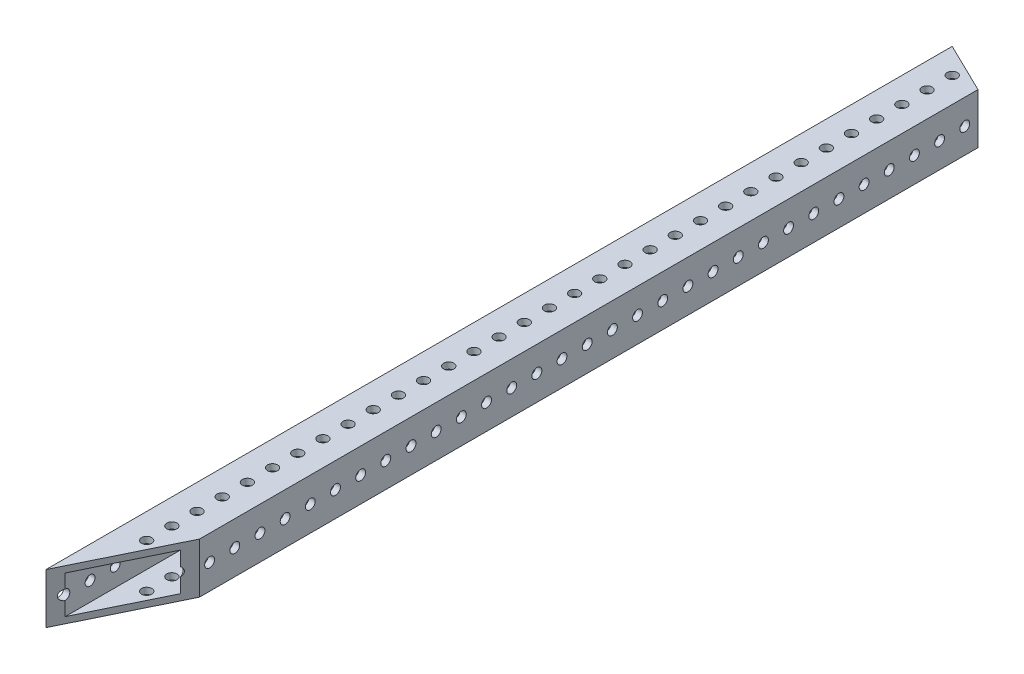
SolidWorks part; units mm, degrees
material "6061-T6 (SS)"
ref_plane "Front Plane" through (0, 0, 0) normal (0, 0, 1) x (1, 0, 0)
ref_plane "Top Plane" through (0, 0, 0) normal (0, 1, 0) x (1, 0, 0)
ref_plane "Right Plane" through (0, 0, 0) normal (1, 0, 0) x (0, 0, -1)
sketch "Sketch1" plane through (0, 0, 0) normal (0, 0, 1) x (1, 0, 0)
  line L0 (-9.525, 9.525) -> (9.525, 9.525)
  line L1 (-12.7, 12.7) -> (12.7, 12.7)
  line L2 (-12.7, 12.7) -> (-12.7, -12.7)
  line L3 (-12.7, -12.7) -> (12.7, -12.7)
  line L4 (12.7, 12.7) -> (12.7, -12.7)
  line L5 (9.525, 9.525) -> (9.525, -9.525)
  line L6 (-9.525, -9.525) -> (9.525, -9.525)
  line L7 (-9.525, 9.525) -> (-9.525, -9.525)
  line L8 (-12.7, 12.7) -> (12.7, -12.7) construction
  line L9 (12.7, 12.7) -> (-12.7, -12.7) construction
  point P5 (0, 0)
  dimension "D1" = 25.4
  dimension "D2" = 25.4
  dimension "D3" = 3.175
extrude "Boss-Extrude1" add sketch "Sketch1" along normal mid plane 457.2
sketch "Sketch2" plane through (0, 12.7, 0) normal (0, 1, 0) x (1, 0, 0)
  circle A2 centre (0, -292.1) radius 2.5527 construction
  circle A3 centre (0, -279.4) radius 2.5527 construction
  circle A6 centre (0, -266.7) radius 2.5527
  circle A9 centre (0, -254) radius 2.5527
  circle A12 centre (0, -241.3) radius 2.5527
  circle A15 centre (0, -228.6) radius 2.5527 construction
  circle A18 centre (0, -215.9) radius 2.5527 construction
  circle A21 centre (0, -203.2) radius 2.5527 construction
  circle A24 centre (0, -190.5) radius 2.5527
  circle A27 centre (0, -177.8) radius 2.5527
  circle A30 centre (0, -165.1) radius 2.5527
  circle A33 centre (0, -152.4) radius 2.5527
  circle A36 centre (0, -139.7) radius 2.5527
  circle A39 centre (0, -127) radius 2.5527
  circle A42 centre (0, -114.3) radius 2.5527
  circle A45 centre (0, -101.6) radius 2.5527
  circle A48 centre (0, -88.9) radius 2.5527
  circle A51 centre (0, -76.2) radius 2.5527
  circle A54 centre (0, -63.5) radius 2.5527
  circle A57 centre (0, -50.8) radius 2.5527
  circle A60 centre (0, -38.1) radius 2.5527
  circle A63 centre (0, -25.4) radius 2.5527
  circle A66 centre (0, -12.7) radius 2.5527
  circle A69 centre (0, 0) radius 2.5527
  circle A72 centre (0, 12.7) radius 2.5527
  circle A75 centre (0, 25.4) radius 2.5527
  circle A78 centre (0, 38.1) radius 2.5527
  circle A81 centre (0, 50.8) radius 2.5527
  circle A84 centre (0, 63.5) radius 2.5527
  circle A87 centre (0, 76.2) radius 2.5527
  circle A90 centre (0, 88.9) radius 2.5527
  circle A93 centre (0, 101.6) radius 2.5527
  circle A96 centre (0, 114.3) radius 2.5527
  circle A99 centre (0, 127) radius 2.5527
  circle A108 centre (0, 152.4) radius 2.5527 [skipped]
  circle A111 centre (0, 139.7) radius 2.5527 [skipped]
  circle A116 centre (0, 139.7) radius 2.5527
  circle A119 centre (0, 152.4) radius 2.5527
  circle A122 centre (0, 165.1) radius 2.5527
  circle A125 centre (0, 177.8) radius 2.5527
  circle A128 centre (0, 190.5) radius 2.5527
  circle A131 centre (0, 203.2) radius 2.5527
  circle A134 centre (0, 215.9) radius 2.5527
  circle A137 centre (0, 228.6) radius 2.5527
  circle A140 centre (0, 241.3) radius 2.5527
  circle A143 centre (0, 254) radius 2.5527
  circle A146 centre (0, 266.7) radius 2.5527
  circle A149 centre (0, 279.4) radius 2.5527
  circle A152 centre (0, 292.1) radius 2.5527
  dimension "D6" = 12.7
  dimension "D5" = 36
  dimension "D8" = 14
extrude "Cut-Extrude1" cut sketch "Sketch2" against normal through all
sketch "Sketch4" plane through (12.7, 0, 0) normal (1, 0, 0) x (0, 0, -1)
  line L1 (-228.6, -12.7) -> (-228.6, 12.7) construction
  line L2 (-228.6, -12.7) -> (228.6, -12.7) construction
  circle A2 centre (-222.25, 0) radius 2.4892
  circle A3 centre (-209.55, 0) radius 2.4892
  circle A16 centre (-196.85, 0) radius 2.4892
  circle A17 centre (-184.15, 0) radius 2.4892
  circle A18 centre (-171.45, 0) radius 2.4892
  circle A19 centre (209.55, 0) radius 2.4892
  circle A20 centre (222.25, 0) radius 2.4892
  circle A21 centre (234.95, 0) radius 2.4892
  circle A22 centre (247.65, 0) radius 2.4892
  circle A23 centre (260.35, 0) radius 2.4892
  circle A24 centre (273.05, 0) radius 2.4892
  circle A25 centre (285.75, 0) radius 2.4892
  circle A26 centre (298.45, 0) radius 2.4892
  circle A27 centre (311.15, 0) radius 2.4892
  circle A28 centre (323.85, 0) radius 2.4892
  circle A29 centre (336.55, 0) radius 2.4892
  circle A30 centre (349.25, 0) radius 2.4892
  circle A31 centre (361.95, 0) radius 2.4892
  circle A32 centre (374.65, 0) radius 2.4892
  circle A35 centre (-158.75, 0) radius 2.4892
  circle A36 centre (-146.05, 0) radius 2.4892
  circle A37 centre (-133.35, 0) radius 2.4892
  circle A38 centre (-120.65, 0) radius 2.4892
  circle A39 centre (-107.95, 0) radius 2.4892
  circle A40 centre (-95.25, 0) radius 2.4892
  circle A41 centre (-82.55, 0) radius 2.4892
  circle A42 centre (-69.85, 0) radius 2.4892
  circle A43 centre (-57.15, 0) radius 2.4892
  circle A44 centre (-44.45, 0) radius 2.4892
  circle A45 centre (-31.75, 0) radius 2.4892
  circle A46 centre (-19.05, 0) radius 2.4892
  circle A47 centre (-6.35, 0) radius 2.4892
  circle A48 centre (6.35, 0) radius 2.4892
  circle A49 centre (19.05, 0) radius 2.4892
  circle A50 centre (31.75, 0) radius 2.4892
  circle A51 centre (44.45, 0) radius 2.4892
  circle A52 centre (57.15, 0) radius 2.4892
  circle A53 centre (69.85, 0) radius 2.4892
  circle A54 centre (82.55, 0) radius 2.4892
  circle A55 centre (95.25, 0) radius 2.4892
  circle A56 centre (107.95, 0) radius 2.4892
  circle A57 centre (120.65, 0) radius 2.4892
  circle A58 centre (133.35, 0) radius 2.4892
  circle A59 centre (146.05, 0) radius 2.4892
  circle A60 centre (158.75, 0) radius 2.4892
  circle A61 centre (171.45, 0) radius 2.4892
  circle A62 centre (184.15, 0) radius 2.4892
  circle A63 centre (196.85, 0) radius 2.4892
  dimension "D2" = 4.9784
  dimension "D1" = 6.35
  dimension "D3" = 12.7
  dimension "D4" = 12.7
  dimension "D5" = 34
  dimension "D6" = 10
  dimension "D7" = 6
extrude "Cut-Extrude3" cut sketch "Sketch4" against normal through all
sketch "Sketch6" plane through (0, 12.7, 0) normal (0, 1, 0) x (1, 0, 0)
  line L4 (-12.7, -228.6) -> (12.7, -176.5223)
  line L5 (12.7, -228.6) -> (12.7, 228.6) construction
  line L6 (12.7, -176.5223) -> (12.7, -228.6)
  line L7 (12.7, -228.6) -> (-12.7, -228.6)
  dimension "D2" = 64
sketch "Sketch7" plane through (0, 12.7, 0) normal (0, 1, 0) x (1, 0, 0)
  line L0 (-12.7, 228.6) -> (12.7, 216.2116)
  line L1 (12.7, -228.6) -> (12.7, 228.6) construction
  line L2 (12.7, 216.2116) -> (12.7, 228.6)
  line L3 (12.7, 228.6) -> (-12.7, 228.6)
  dimension "D1" = 26
extrude "Cut-Extrude4" cut sketch "Sketch6" against normal through all
extrude "Cut-Extrude5" cut sketch "Sketch7" against normal through all
